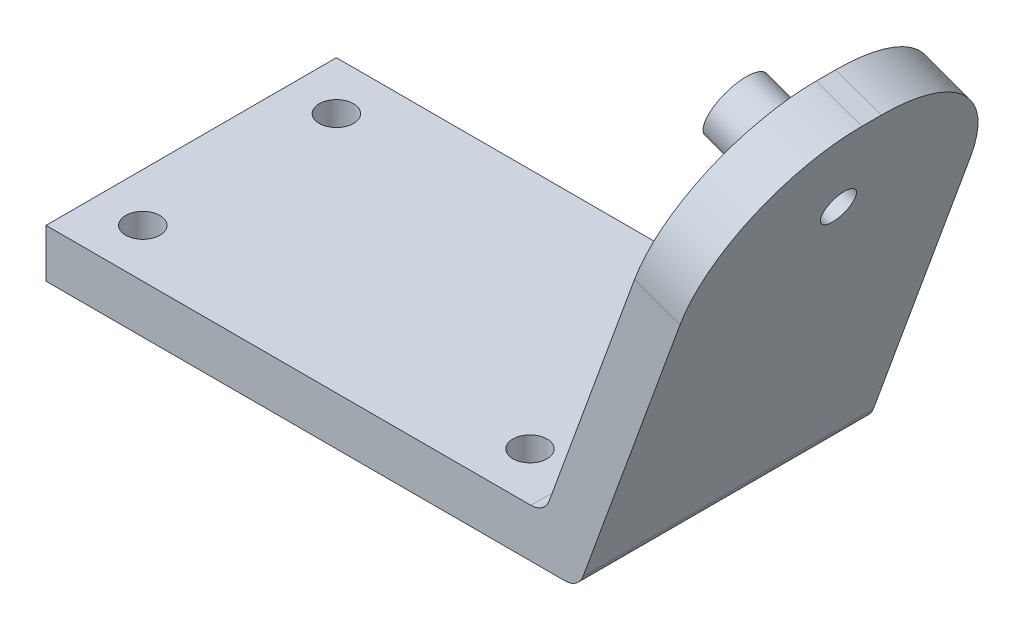
SolidWorks part; units mm, degrees
ref_plane "Front Plane" through (0, 0, 0) normal (0, 0, 1) x (1, 0, 0)
ref_plane "Top Plane" through (0, 0, 0) normal (0, 1, 0) x (1, 0, 0)
ref_plane "Right Plane" through (0, 0, 0) normal (1, 0, 0) x (0, 0, -1)
sketch "Sketch1" plane through (0, 0, 0) normal (0, 1, 0) x (1, 0, 0)
  line L1 (-34.925, -19.05) -> (34.925, -19.05)
  line L2 (-34.925, -19.05) -> (-34.925, 19.05)
  line L3 (-34.925, 19.05) -> (34.925, 19.05)
  line L4 (34.925, -19.05) -> (34.925, 19.05)
  line L5 (-34.925, -19.05) -> (34.925, 19.05) construction
  line L6 (-34.925, 19.05) -> (34.925, -19.05) construction
  point P0 (0, 0)
  dimension "D1" = 69.85
  dimension "D2" = 38.1
extrude "Boss-Extrude1" add sketch "Sketch1" along normal blind 6.35
sketch "Sketch2" plane through (0, 0, 19.05) normal (0, 0, 1) x (1, 0, 0)
  line L0 (34.925, 0) -> (54.3405, 53.3436)
  line L1 (34.925, 0) -> (28.958, 2.1718)
  line L2 (54.3405, 53.3436) -> (48.3734, 55.5154)
  line L3 (28.958, 2.1718) -> (48.3734, 55.5154)
  line L4 (34.925, 0) -> (48.3734, 55.5154) construction
  line L5 (54.3405, 53.3436) -> (28.958, 2.1718) construction
  line L6 (34.925, 6.35) -> (34.925, 0) construction
  line L7 (-34.925, 0) -> (34.925, 0) construction
  point P1 (41.6492, 27.7577)
  dimension "D1" = 20
  dimension "D2" = 50.8
extrude "Boss-Extrude2" add sketch "Sketch2" against normal up to surface (38.1 mm away) up to face at (0, 3.175, -19.05)
sketch "Sketch3" plane through (24.8725, -9.0529, 0) normal (-0.9397, 0.342, 0) x (0, 0, 1)
  line L0 (0, 56.0121) -> (0, 68.7121) construction
  line L1 (-19.05, 68.7121) -> (19.05, 68.7121) construction
  circle A0 centre (0, 56.0121) radius 2.25
  dimension "D2" = 4.5
  dimension "D1" = 12.7
extrude "Cut-Extrude1" cut sketch "Sketch3" against normal through all
fillet "Fillet1" radius 17.78 2 edges at (51.3569, 54.4295, 19.05) (51.3569, 54.4295, -19.05)
sketch "Sketch4" plane through (0, 6.35, 0) normal (0, 1, 0) x (1, 0, 0)
  circle A0 centre (22.225, -12.7) radius 2.25 construction
  circle A1 centre (-28.575, -12.7) radius 2.25 construction
  circle A2 centre (22.225, 12.7) radius 2.25 construction
  circle A3 centre (-28.575, 12.7) radius 2.25 construction
  circle A4 centre (22.225, -12.7) radius 2.25
  circle A5 centre (-28.575, -12.7) radius 2.25
  circle A6 centre (22.225, 12.7) radius 2.25
  circle A7 centre (-28.575, 12.7) radius 2.25
extrude "Cut-Extrude2" cut sketch "Sketch4" against normal through all
sketch "Sketch5" plane through (24.8725, -9.0529, 0) normal (-0.9397, 0.342, 0) x (0, 0, 1)
  circle A0 centre (0, 56.0121) radius 5
  circle M1 centre (0, 56.0121) radius 2.25
  dimension "D1" = 10
extrude "Boss-Extrude3" add sketch "Sketch5" along normal blind 1 contours A0 M1 region at (44.0298, 43.5813, -4.8586)
sketch "Sketch6" plane through (23.9328, -8.7108, 0) normal (-0.9397, 0.342, 0) x (0, 0, 1)
  circle A0 centre (0, 56.0121) radius 4.05
  circle M2 centre (0, 56.0121) radius 2.25
  dimension "D1" = 8.1
extrude "Boss-Extrude4" add sketch "Sketch6" along normal blind 7 contours A0 M2 region at (43.0901, 43.9233, -3.9355)
fillet "Fillet2" radius 2.54 2 edges at (34.925, 0, 0) (30.4787, 6.35, 0)
